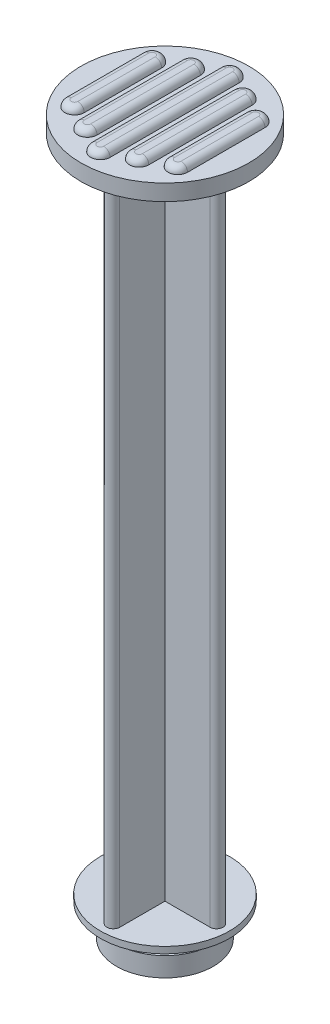
SolidWorks part; units mm, degrees
ref_plane "Front Plane" through (0, 0, 0) normal (0, 0, 1) x (1, 0, 0)
ref_plane "Top Plane" through (0, 0, 0) normal (0, 1, 0) x (1, 0, 0)
ref_plane "Right Plane" through (0, 0, 0) normal (1, 0, 0) x (0, 0, -1)
sketch "Sketch3" plane through (0, 0, 0) normal (0, 0, 1) x (1, 0, 0)
  line L0 (0, 0) -> (7.5, 0)
  line L1 (7.5, 0) -> (7.5, 3)
  line L2 (7.5, 3) -> (6, 3)
  line L3 (6, 3) -> (6, 5)
  line L4 (6, 5) -> (10, 5)
  line L5 (10, 5) -> (10, 6)
  line L6 (10, 6) -> (0, 6)
  line L7 (0, 6) -> (0, 0)
  dimension "D1" = 10
  dimension "D2" = 3
  dimension "D3" = 2
  dimension "D4" = 1
  dimension "D5" = 7.5
  dimension "D6" = 1.5
revolve "Revolve1" add sketch "Sketch3" angle 360 about L7
sketch "Sketch4" plane through (0, 6, 0) normal (0, 1, 0) x (1, 0, 0)
  line L0 (0, 10) -> (0, -10) construction
  line L1 (-10, 0) -> (10, 0) construction
  line L2 (-1, 8) -> (-1, -8)
  line L3 (-8, -1) -> (8, -1)
  line L4 (1, 8) -> (1, -8)
  line L5 (-8, 1) -> (8, 1)
  line L6 (-1, 10) -> (-1, -10) construction
  line L7 (1, 10) -> (1, -10) construction
  line L8 (-10, 1) -> (10, 1) construction
  line L9 (-10, -1) -> (10, -1) construction
  circle A0 centre (0, 0) radius 10 construction
  arc A3 (1, 8) -> (-1, 8) centre (0, 8) ccw
  arc A4 (-8, 1) -> (-8, -1) centre (-8, 0) ccw
  arc A5 (1, -8) -> (-1, -8) centre (0, -8) cw
  arc A6 (8, 1) -> (8, -1) centre (8, 0) cw
  dimension "D3" = 8
  dimension "D4" = 8
  dimension "D1" = 1
  dimension "D2" = 1
extrude "Boss-Extrude5" add sketch "Sketch4" along normal blind 102 contours L4 A3 L2 L5 | L5 A4 L3 L2 | A5 L4 L3 L2 | A6 L5 L4 L3 | L5 L2 L3 L4 region at (0, 6, -4.8959) region at (0, 6, 0) region at (-4.8959, 6, 0) region at (0, 6, 4.8959) region at (4.8959, 6, 0)
sketch "Sketch5" plane through (0, 108, 0) normal (0, 1, 0) x (1, 0, 0)
  circle A0 centre (0, 0) radius 13
  dimension "D1" = 26
extrude "Boss-Extrude6" add sketch "Sketch5" along normal blind 2.5 contours A0
sketch "Sketch8" plane through (0, 110.5, 0) normal (0, 1, 0) x (1, 0, 0)
  line L0 (0, 13) -> (0, -13) construction
  line L1 (-13.114, 0) -> (12.8891, 0) construction
  line L2 (-4, 8) -> (-4, -8) construction
  line L3 (-8, 6) -> (-8, -6) construction
  line L4 (-1.5, 10) -> (-1.5, -10)
  line L5 (-5.5, 8) -> (-5.5, -8)
  line L6 (-9.5, 6) -> (-9.5, -6)
  line L7 (1.5, 10) -> (1.5, -10)
  line L8 (-2.5, 8) -> (-2.5, -8)
  line L9 (-6.5, 6) -> (-6.5, -6)
  line L10 (6.5, 6) -> (6.5, -6)
  line L11 (9.5, 6) -> (9.5, -6)
  line L12 (5.5, 8) -> (5.5, -8)
  line L13 (2.5, 8) -> (2.5, -8)
  circle A0 centre (0, 0) radius 13 construction
  arc A1 (-6.5, 6) -> (-9.5, 6) centre (-8, 6) ccw
  arc A2 (-2.5, 8) -> (-5.5, 8) centre (-4, 8) ccw
  arc A3 (1.5, 10) -> (-1.5, 10) centre (0, 10) ccw
  arc A4 (-9.5, -6) -> (-6.5, -6) centre (-8, -6) ccw
  arc A5 (-5.5, -8) -> (-2.5, -8) centre (-4, -8) ccw
  arc A6 (-1.5, -10) -> (1.5, -10) centre (0, -10) ccw
  arc A7 (6.5, 6) -> (9.5, 6) centre (8, 6) cw
  arc A8 (9.5, -6) -> (6.5, -6) centre (8, -6) cw
  arc A9 (2.5, 8) -> (5.5, 8) centre (4, 8) cw
  arc A10 (5.5, -8) -> (2.5, -8) centre (4, -8) cw
  point P12 (-25.6294, 17.9797)
extrude "Boss-Extrude7" add sketch "Sketch8" along normal blind 1
fillet "Fillet1" radius 1 20 edges at (9.5, 111.5, 0) (8, 111.5, 7.5) (6.5, 111.5, 0) (8, 111.5, -7.5) (5.5, 111.5, 0) (4, 111.5, 9.5) (2.5, 111.5, 0) (4, 111.5, -9.5) (1.5, 111.5, 0) (0, 111.5, 11.5) (-1.5, 111.5, 0) (0, 111.5, -11.5) (-2.5, 111.5, 0) (-4, 111.5, 9.5) (-5.5, 111.5, 0) (-4, 111.5, -9.5) (-6.5, 111.5, 0) (-8, 111.5, 7.5) (-9.5, 111.5, 0) (-8, 111.5, -7.5)
